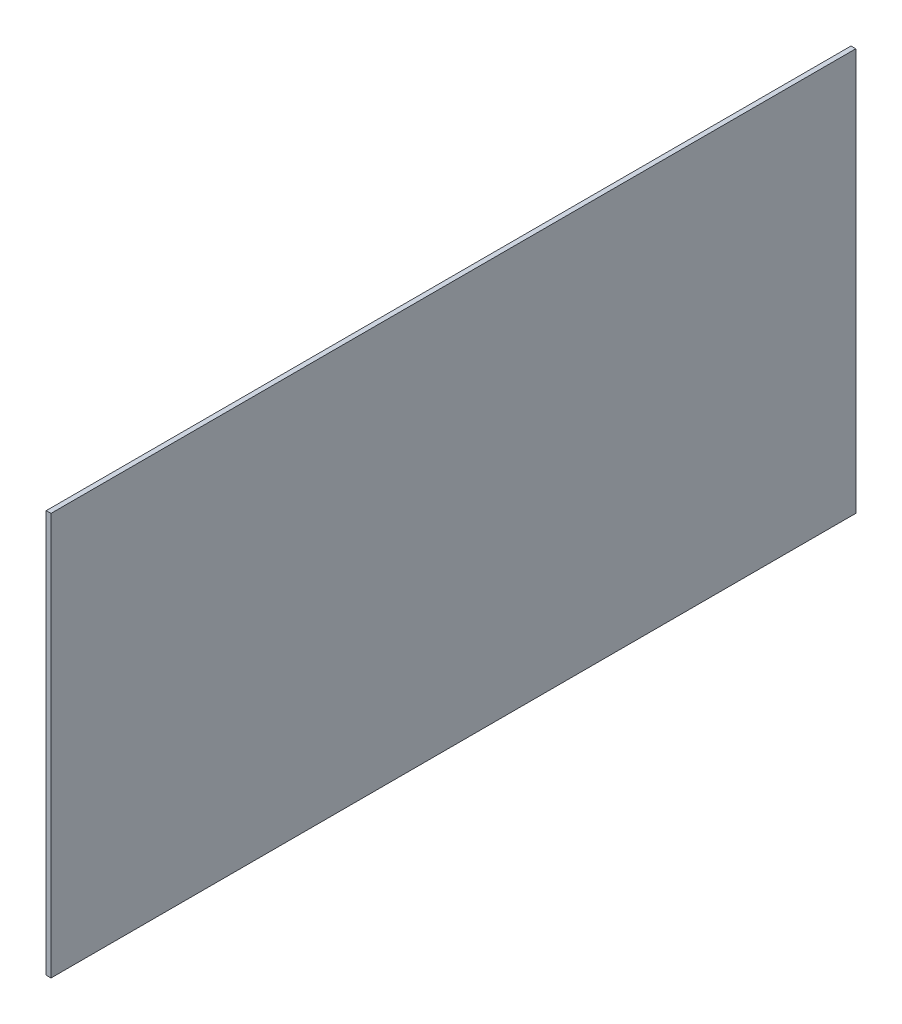
SolidWorks part; units mm, degrees
ref_plane "Front Plane" through (0, 0, 0) normal (0, 0, 1) x (1, 0, 0)
ref_plane "Top Plane" through (0, 0, 0) normal (0, 1, 0) x (1, 0, 0)
ref_plane "Right Plane" through (0, 0, 0) normal (1, 0, 0) x (0, 0, -1)
sketch "Sketch1" plane through (0, 0, 0) normal (1, 0, 0) x (0, 0, -1)
  line L1 (0, 0) -> (266.7, 0)
  line L2 (0, 0) -> (0, 133.35)
  line L3 (0, 133.35) -> (266.7, 133.35)
  line L4 (266.7, 0) -> (266.7, 133.35)
  dimension "D1" = 133.35
  dimension "D2" = 266.7
extrude "Boss-Extrude1" add sketch "Sketch1" along normal blind 1.5875
